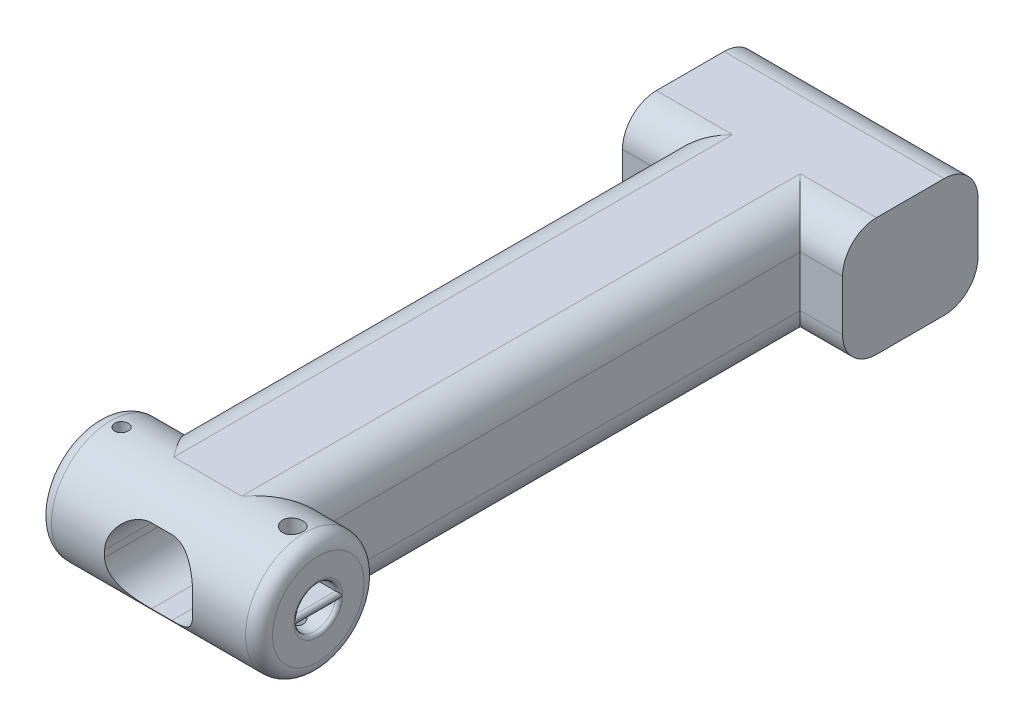
SolidWorks part; units mm, degrees
material "PVC Rigid"
ref_plane "Alzado" through (0, 0, 0) normal (0, 0, 1) x (1, 0, 0)
ref_plane "Planta" through (0, 0, 0) normal (0, 1, 0) x (1, 0, 0)
ref_plane "Vista lateral" through (0, 0, 0) normal (1, 0, 0) x (0, 0, -1)
sketch "Croquis1" plane through (0, 0, 10.8518) normal (1, 0, 0) x (0, 0, -1)
  circle A0 centre (0, 0) radius 8.75
extrude "Saliente-Extruir1" add sketch "Croquis1" along normal blind 32.6517
sketch "Sketch2" plane through (32.6517, 0, 0) normal (1, 0, 0) x (0, 0, -1)
  line L1 (-13.9104, 0.505) -> (-7.7932, 0.505)
  line L3 (-13.9104, -0.505) -> (-7.7932, -0.505)
  arc A0 (-7.7932, 0.505) -> (-13.9104, 0.505) centre (-10.8518, 0) ccw
  arc A1 (-13.9104, -0.505) -> (-7.7932, -0.505) centre (-10.8518, 0) ccw
extrude "Cut-Extrude1" cut sketch "Sketch2" against normal blind 7
fillet "Fillet4" radius 0.5 2 edges at (32.6517, -0.505, 10.8518) (32.6517, 0.505, 10.8518)
fillet "Fillet5" radius 0.5 2 edges at (32.6517, -3.1, 10.8518) (32.6517, 3.1, 10.8518)
sketch "Sketch3" plane through (0, 0, 0) normal (-1, 0, 0) x (0, 0, 1)
  line L1 (9.0672, 1.8214) -> (12.6364, 1.8214)
  line L3 (9.0672, -1.8214) -> (12.6364, -1.8214)
  arc A0 (9.0672, 1.8214) -> (9.0672, -1.8214) centre (10.8518, 0) ccw
  arc A1 (12.6364, -1.8214) -> (12.6364, 1.8214) centre (10.8518, 0) ccw
extrude "Cut-Extrude2" cut sketch "Sketch3" against normal blind 7.5
fillet "Fillet7" radius 0.5 4 edges at (0, 0, 8.3018) (0, -1.8214, 10.8518) (0, 0, 13.4018) (0, 1.8214, 10.8518)
fillet "Fillet9" radius 2 2 edges at (32.6517, 0, 2.1018) (0, 0, 2.1018)
sketch "Sketch12" plane through (0, -1.8214, 0) normal (0, 1, 0) x (1, 0, 0)
  circle A0 centre (3.6124, -10.8518) radius 1
  circle A1 centre (28.8837, -10.8518) radius 1.5
extrude "Cut-Extrude3" cut sketch "Sketch12" against normal blind 7.5 and the other way blind 13.5
ref_plane "Plane1" through (16.3258, 0, 0) normal (1, 0, 0) x (0, 0, -1)
sketch "Sketch14" plane through (16.3258, 0, 0) normal (1, 0, 0) x (0, 0, -1)
  line L0 (-14.4518, -0.005) -> (-7.2518, -0.005) construction
  line L5 (-10.8518, 8.75) -> (-10.8518, -8.75)
  line L6 (-10.8518, -8.75) -> (76.6421, -8.75)
  line L7 (76.6421, -8.75) -> (76.6421, 8.75)
  line L12 (76.6421, 8.75) -> (-10.8518, 8.75)
  circle A1 centre (-10.8518, 0) radius 8.75 construction
  point P0 (-10.8518, -0.005)
extrude "Boss-Extrude1" add sketch "Sketch14" along normal blind 10 and the other way blind 10
sketch "Sketch15" plane through (0, 0, -76.6421) normal (0, 0, -1) x (-1, 0, 0)
  line L0 (-16.3258, 7.425) -> (-16.3258, -7.425) construction
  line L1 (-17.8258, 5.5) -> (-14.8258, 5.5)
  line L2 (-22.8258, 0.5) -> (-22.8258, -0.5)
  line L3 (-17.8258, -5.5) -> (-14.8258, -5.5)
  line L4 (-9.8258, 0.5) -> (-9.8258, -0.5)
  line L5 (-22.8258, 5.5) -> (-9.8258, -5.5) construction
  line L6 (-22.8258, -5.5) -> (-9.8258, 5.5) construction
  arc A0 (-22.8258, 0.5) -> (-17.8258, 5.5) centre (-17.8258, 0.5) cw
  arc A1 (-22.8258, -0.5) -> (-17.8258, -5.5) centre (-17.8258, -0.5) ccw
  arc A2 (-14.8258, -5.5) -> (-9.8258, -0.5) centre (-14.8258, -0.5) ccw
  arc A3 (-14.8258, 5.5) -> (-9.8258, 0.5) centre (-14.8258, 0.5) cw
  point P0 (-16.3258, 0)
  dimension "D1" = 5
  dimension "D2" = 5
  dimension "D3" = 13
  dimension "D4" = 11
sketch "Sketch16" plane through (0, 8.75, 0) normal (0, 1, 0) x (1, 0, 0)
  line L0 (6.3258, 76.6421) -> (26.3258, 76.6421) construction
  line L1 (0.0758, 86.6421) -> (32.5758, 86.6421)
  line L2 (0.0758, 86.6421) -> (0.0758, 66.6421)
  line L3 (0.0758, 66.6421) -> (32.5758, 66.6421)
  line L4 (32.5758, 86.6421) -> (32.5758, 66.6421)
  line L5 (0.0758, 86.6421) -> (32.5758, 66.6421) construction
  line L6 (0.0758, 66.6421) -> (32.5758, 86.6421) construction
  point P0 (16.3258, 76.6421)
  dimension "D1" = 32.5
  dimension "D2" = 20
extrude "Boss-Extrude2" add sketch "Sketch16" against normal through all
fillet "Fillet11" radius 5 10 edges at (3.2008, 8.75, -66.6421) (3.2008, -8.75, -66.6421) (29.4508, -8.75, -66.6421) (29.4508, 8.75, -66.6421) (16.3258, -8.75, -86.6421) (16.3258, 8.75, -86.6421) (6.3258, -8.75, -27.8951) (6.3258, 8.75, -27.8951) (26.3258, -8.75, -27.8951) (26.3258, 8.75, -27.8951)
sketch "Sketch19" plane through (0, 0, -86.6421) normal (0, 0, -1) x (-1, 0, 0)
  line L1 (-17.8258, 5.5) -> (-14.8258, 5.5)
  line L2 (-22.8258, 0.5) -> (-22.8258, -0.5)
  line L3 (-17.8258, -5.5) -> (-14.8258, -5.5)
  line L4 (-9.8258, 0.5) -> (-9.8258, -0.5)
  line L5 (-22.8258, 5.5) -> (-9.8258, -5.5) construction
  line L6 (-22.8258, -5.5) -> (-9.8258, 5.5) construction
  arc A0 (-22.8258, -0.5) -> (-17.8258, -5.5) centre (-17.8258, -0.5) ccw
  arc A1 (-14.8258, -5.5) -> (-9.8258, -0.5) centre (-14.8258, -0.5) ccw
  arc A2 (-9.8258, 0.5) -> (-14.8258, 5.5) centre (-14.8258, 0.5) ccw
  arc A3 (-17.8258, 5.5) -> (-22.8258, 0.5) centre (-17.8258, 0.5) ccw
  point P0 (-16.3258, 0)
  dimension "D1" = 5
extrude "Cut-Extrude6" cut sketch "Sketch19" against normal blind 150
sketch "Sketch20" plane through (0, 0, -86.6421) normal (0, 0, -1) x (-1, 0, 0)
  circle A0 centre (-16.3258, 0) radius 3
sketch "Sketch21" plane through (0.0758, 0, 0) normal (-1, 0, 0) x (0, 0, 1)
  circle A0 centre (-76.6421, 0) radius 4
extrude "Cut-Extrude7" cut sketch "Sketch21" against normal blind 5
